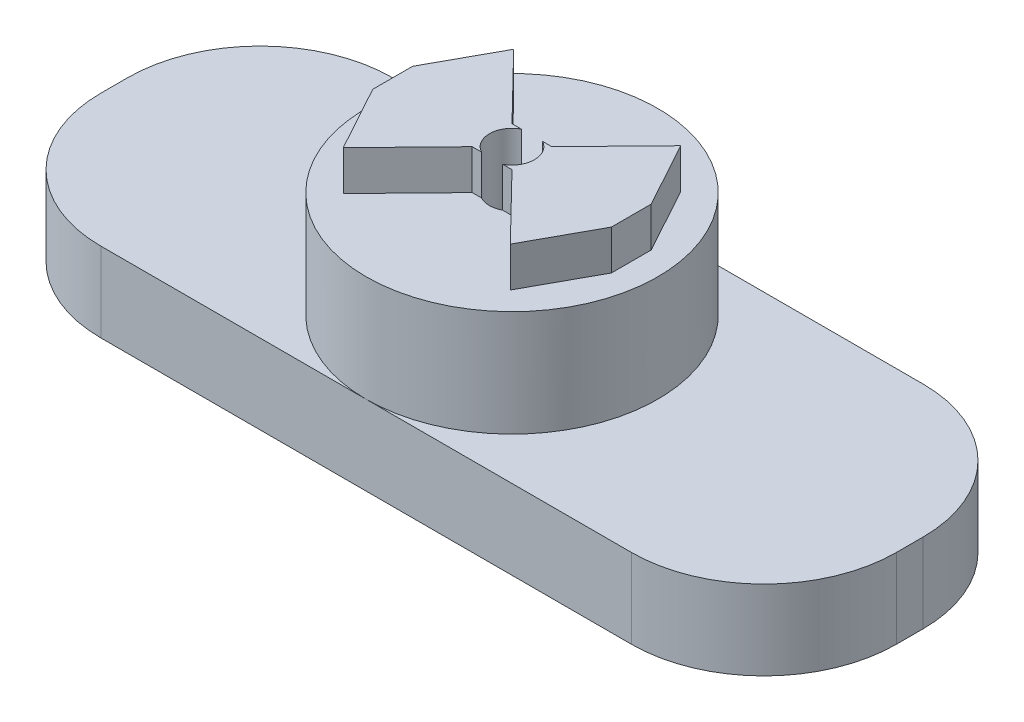
SolidWorks part; units mm, degrees
ref_plane "Płaszczyzna przednia" through (0, 0, 0) normal (0, 0, 1) x (1, 0, 0)
ref_plane "Płaszczyzna górna" through (0, 0, 0) normal (0, 1, 0) x (1, 0, 0)
ref_plane "Płaszczyzna prawa" through (0, 0, 0) normal (1, 0, 0) x (0, 0, -1)
sketch "Sketch1" plane through (0, 0, 0) normal (0, 1, 0) x (1, 0, 0)
  line L5 (-20.01, -11) -> (20.01, -11)
  line L6 (-30, -1.01) -> (-30, 1.01)
  line L7 (-20.01, 11) -> (20.01, 11)
  line L8 (30, -1.01) -> (30, 1.01)
  line L9 (-30, -11) -> (30, 11) construction
  line L10 (-30, 11) -> (30, -11) construction
  arc A0 (-20.01, -11) -> (-30, -1.01) centre (-20.01, -1.01) cw
  arc A1 (20.01, -11) -> (30, -1.01) centre (20.01, -1.01) ccw
  arc A2 (20.01, 11) -> (30, 1.01) centre (20.01, 1.01) cw
  arc A3 (-30, 1.01) -> (-20.01, 11) centre (-20.01, 1.01) cw
  point P0 (0, 0)
  point P1 (0, 0)
  dimension "D3" = 9.99
  dimension "D1" = 60
  dimension "D2" = 22
extrude "Boss-Extrude1" add sketch "Sketch1" along normal blind 6
sketch "Sketch2" plane through (0, 6, 0) normal (0, 1, 0) x (1, 0, 0)
  line L0 (0, 0) -> (-3, 0) construction
  line L1 (0, 0) -> (3, 0) construction
  circle A3 centre (0, 0) radius 11
extrude "Boss-Extrude2" add sketch "Sketch2" along normal blind 8
sketch "Sketch12" plane through (0, 0, 0) normal (0, -1, 0) x (1, 0, 0)
  circle A0 centre (0, 0) radius 6
extrude "Cut-Extrude2" cut sketch "Sketch12" against normal blind 4
sketch "Sketch18" plane through (0, 4, 0) normal (0, -1, 0) x (-1, 0, 0)
  point P0 (0, 0)
sketch "Sketch19" plane through (0, 14, 0) normal (0, 1, 0) x (1, 0, 0)
  line L26 (-6.3004, 6.4269) -> (-9, 1.5)
  line L27 (-1.5, -1.5) -> (1.5, -1.5) construction
  line L28 (-1.5, -1.5) -> (-1.5, 1.5) construction
  line L29 (-1.5, 1.5) -> (1.5, 1.5) construction
  line L30 (1.5, -1.5) -> (1.5, 1.5) construction
  line L31 (-1.5, -1.5) -> (1.5, 1.5) construction
  line L32 (-1.5, 1.5) -> (1.5, -1.5) construction
  line L33 (-6.3004, -6.4269) -> (6.3004, -6.4269) construction
  line L34 (-6.3004, -6.4269) -> (-6.3004, 6.4269) construction
  line L35 (-6.3004, 6.4269) -> (6.3004, 6.4269) construction
  line L36 (6.3004, -6.4269) -> (6.3004, 6.4269) construction
  line L37 (-6.3004, -6.4269) -> (6.3004, 6.4269) construction
  line L38 (-6.3004, 6.4269) -> (6.3004, -6.4269) construction
  line L39 (-9, -1.5) -> (9, -1.5) construction
  line L40 (-9, -1.5) -> (-9, 1.5) construction
  line L41 (-9, 1.5) -> (9, 1.5) construction
  line L42 (9, -1.5) -> (9, 1.5) construction
  line L43 (-9, -1.5) -> (9, 1.5) construction
  line L44 (-9, 1.5) -> (9, -1.5) construction
  line L45 (-9, 1.5) -> (-9, -1.5)
  line L46 (-9, -1.5) -> (-6.3004, -6.4269)
  line L47 (-6.3004, -6.4269) -> (-1.5, -1.5)
  line L48 (-1.5, -1.5) -> (1.5, -1.5)
  line L49 (1.5, -1.5) -> (6.3004, -6.4269)
  line L50 (6.3004, -6.4269) -> (9, -1.5)
  line L51 (9, -1.5) -> (9, 1.5)
  line L52 (9, 1.5) -> (6.3004, 6.4269)
  line L53 (6.3004, 6.4269) -> (1.5, 1.5)
  line L54 (1.5, 1.5) -> (-1.5, 1.5)
  line L55 (-1.5, 1.5) -> (-6.3004, 6.4269)
  point P16 (0, 0)
  point P22 (0, 0)
  point P27 (0, 0)
  dimension "D1" = 12.6008
  dimension "D2" = 12.8538
  dimension "D4" = 3
  dimension "D5" = 3
  dimension "D6" = 18
  dimension "D7" = 18
extrude "Boss-Extrude3" add sketch "Sketch19" along normal blind 3
hole_wizard "CSK for M3 Countersunk Flat Head Screw3" positions "Sketch18" profile "Sketch17" countersink size "M3" standard "ISO" end condition through all
sketch "Sketch17" plane through (0, 4, 0) normal (1, 0, 0) x (0, 0, -1)
  line L0 (0, 0) -> (0, 13)
  line L1 (0, 13) -> (1.7, 13)
  line L2 (1.7, 13) -> (1.7, 1.45)
  line L3 (1.7, 1.45) -> (3.15, 0)
  line L5 (3.15, 0) -> (0, 0)
  line L6 (-1.7, 1.45) -> (-3.15, 0) construction
  line L11 (0, -6.35) -> (0, 107.95) construction
  dimension "Thru Hole Dia." = 3.4
  dimension "Thru Hole Depth" = 13
  dimension "Near C'Sink Dia." = 6.3
  dimension "Near C'Sink Angle" = 90
